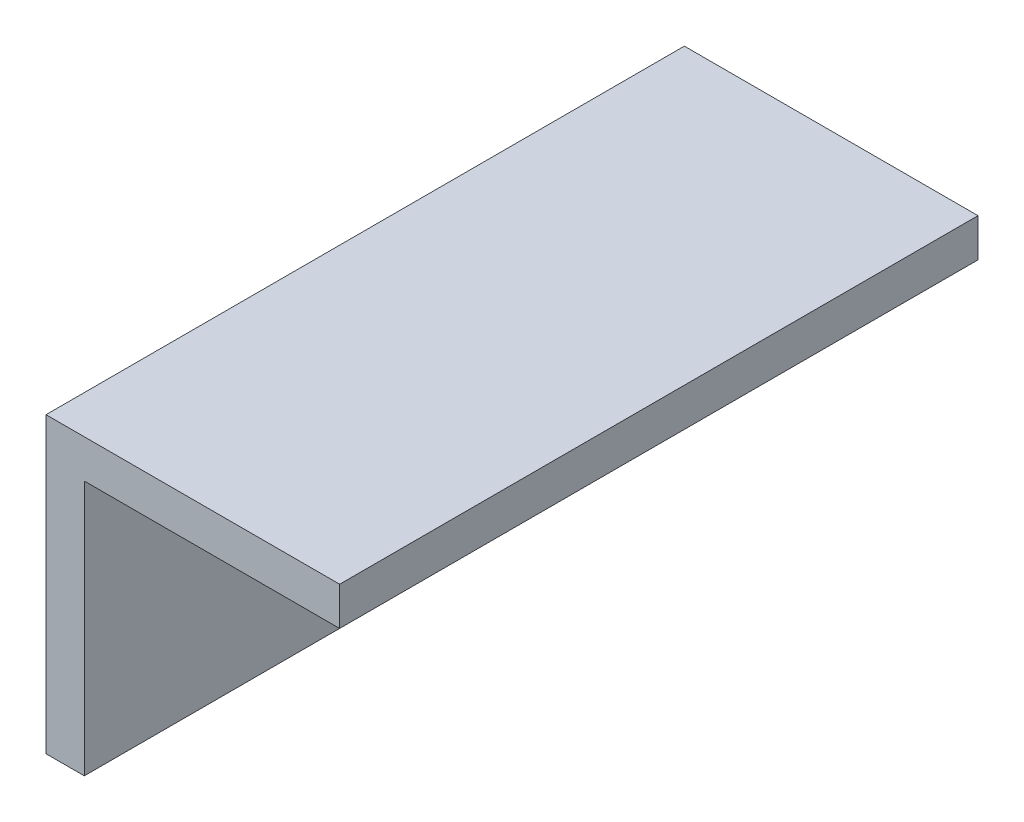
SolidWorks part; units mm, degrees
material "PLA"
ref_plane "Front Plane" through (0, 0, 0) normal (0, 0, 1) x (1, 0, 0)
ref_plane "Top Plane" through (0, 0, 0) normal (0, 1, 0) x (1, 0, 0)
ref_plane "Right Plane" through (0, 0, 0) normal (1, 0, 0) x (0, 0, -1)
sketch "Sketch1" plane through (0, 0, 0) normal (0, 0, 1) x (1, 0, 0)
  line L0 (0, 0) -> (40, 0)
  line L1 (0, 0) -> (0, -40)
  line L2 (-6, 6) -> (-6, -40)
  line L3 (-6, 6) -> (40, 6)
  line L4 (0, -40) -> (-6, -40)
  line L5 (40, 0) -> (40, 6)
  dimension "D1" = 40
  dimension "D2" = 40
  dimension "D3" = 6
extrude "Boss-Extrude1" add sketch "Sketch1" along normal mid plane 100
